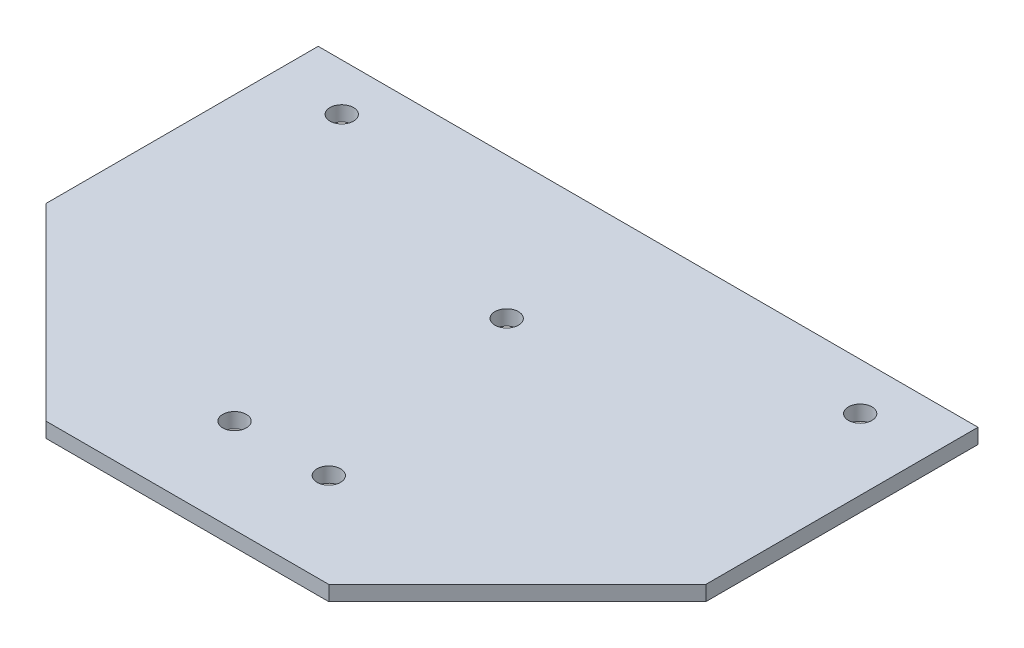
SolidWorks part; units mm, degrees
ref_plane "Front Plane" through (0, 0, 0) normal (0, 0, 1) x (1, 0, 0)
ref_plane "Top Plane" through (0, 0, 0) normal (0, 1, 0) x (1, 0, 0)
ref_plane "Right Plane" through (0, 0, 0) normal (1, 0, 0) x (0, 0, -1)
sketch "Sketch1" plane through (0, 0, 0) normal (0, 1, 0) x (1, 0, 0)
  line L0 (0, 0) -> (40, 0)
  line L1 (40, 0) -> (90, 0)
  line L2 (90, 97.7514) -> (90, 57.7514)
  line L3 (90, 97.7514) -> (-50, 97.7514)
  line L4 (-50, 97.7514) -> (-50, 0)
  line L5 (90, 57.7514) -> (90, 40)
  line L6 (90, 40) -> (90, 0)
  line L7 (90, 40) -> (-50, 40) construction
  line L8 (90, 57.7514) -> (-50, 57.7514) construction
  line L9 (30, 0) -> (30, 40) construction
  line L10 (10, 40) -> (10, 0) construction
  line L11 (90, 87.7514) -> (-50, 87.7514) construction
  line L12 (90, 67.7514) -> (-50, 67.7514) construction
  line L13 (-50, 0) -> (0, 0)
  circle A0 centre (-35, 87.7514) radius 2.5
  circle A1 centre (75, 87.7514) radius 2.5
  circle A2 centre (20, 67.7514) radius 2.5
  circle A3 centre (10, 20) radius 2.5
  circle A4 centre (30, 20) radius 2.5
  dimension "D7" = 10
  dimension "D9" = 5
  dimension "D2" = 40
  dimension "D3" = 40
  dimension "D5" = 40
  dimension "D6" = 50
  dimension "D8" = 10
  dimension "D10" = 10
  dimension "D11" = 10
  dimension "D12" = 15
  dimension "D13" = 15
extrude "Boss-Extrude1" add sketch "Sketch1" along normal blind 3.18
sketch "Sketch3" plane through (0, 0, 0) normal (0, -1, 0) x (1, 0, 0)
  line L0 (90, -40) -> (50, 0)
  line L1 (90, 0) -> (90, -97.7514) construction
  line L2 (-50, 0) -> (90, 0) construction
  line L3 (50, 0) -> (90, 0)
  line L4 (90, 0) -> (90, -40)
  line L5 (-50, 0) -> (-10, 0)
  line L6 (-50, 0) -> (90, 0) construction
  line L7 (-10, 0) -> (-50, -40)
  line L8 (-50, -97.7514) -> (-50, 0) construction
  line L9 (-50, -40) -> (-50, 0)
  line L10 (90, -40) -> (-50, -40) construction
  dimension "D1" = 40
  dimension "D2" = 40
extrude "Cut-Extrude1" cut sketch "Sketch3" against normal through all
